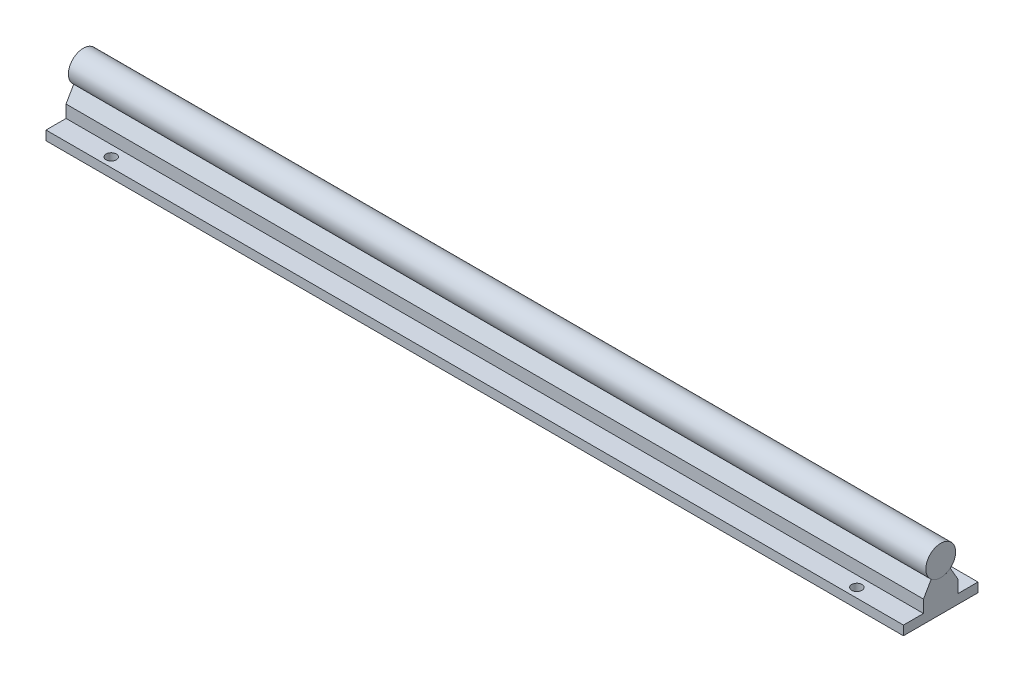
SolidWorks part; units mm, degrees
ref_plane "Спереди" through (0, 0, 0) normal (0, 0, 1) x (1, 0, 0)
ref_plane "Сверху" through (0, 0, 0) normal (0, 1, 0) x (1, 0, 0)
ref_plane "Справа" through (0, 0, 0) normal (1, 0, 0) x (0, 0, -1)
other "Центр тяжести"
sketch "Эскиз3" plane through (0, 0, 0) normal (1, 0, 0) x (0, 0, -1)
  circle A0 centre (0, 0) radius 8
  dimension "D1" = 16
extrude "Вал" add sketch "Эскиз3" along normal blind 460
sketch "Эскиз4" plane through (0, 0, 0) normal (1, 0, 0) x (0, 0, -1)
  line L0 (-9.25, -20) -> (-9.25, -13.3)
  line L1 (-20, -20) -> (-9.25, -20)
  line L2 (-20, -20) -> (-20, -25)
  line L3 (-20, -25) -> (20, -25)
  line L4 (20, -20) -> (20, -25)
  line L5 (-5.1201, -6.1469) -> (-9.25, -13.3)
  line L6 (9.25, -13.3) -> (5.1201, -6.1469)
  line L7 (9.25, -13.3) -> (9.25, -20)
  line L8 (-9.25, -13.3) -> (-20, -20) construction
  line L9 (9.25, -13.3) -> (20, -20) construction
  line L10 (0, 15.2149) -> (0, -37.056) construction
  line L11 (9.25, -20) -> (20, -20)
  line L12 (9.25, -20) -> (0, -20) construction
  line L13 (0, -20) -> (-9.25, -20) construction
  circle A0 centre (0, 0) radius 8 construction
  arc A1 (-5.1201, -6.1469) -> (5.1201, -6.1469) centre (0, 0) ccw
  point P11 (0, -25)
  dimension "D1" = 5
  dimension "D2" = 40
  dimension "D3" = 11.7
  dimension "D4" = 18.5
  dimension "D5" = 30
  dimension "D6" = 25
extrude "Опора" add sketch "Эскиз4" along normal blind 460 separate body
sketch "Эскиз5" plane through (0, -20, 0) normal (0, 1, 0) x (1, 0, 0)
  line L3 (230, 20) -> (230, -20) construction
  line L4 (460, 20) -> (0, 20) construction
  line L5 (460, -20) -> (0, -20) construction
  line L7 (430, -15) -> (30, -15) construction
  line L8 (430, -15) -> (430, 15) construction
  line L9 (430, 15) -> (30, 15) construction
  line L10 (30, -15) -> (30, 15) construction
  line L11 (430, -15) -> (30, 15) construction
  line L12 (430, 15) -> (30, -15) construction
  circle A0 centre (430, 15) radius 2.75
  circle A1 centre (430, -15) radius 2.75
  circle A2 centre (30, -15) radius 2.75
  circle A3 centre (30, 15) radius 2.75
  point P9 (230, 0)
  dimension "D1" = 5.5
  dimension "D2" = 5.5
  dimension "D5" = 5.5
  dimension "D6" = 5.5
  dimension "D3" = 400
  dimension "D4" = 30
extrude "Крепёжные отверстия" cut sketch "Эскиз5" against normal through all
ref_axis "Ось вала" through (495.3685, 0, 0) along (-1, 0, 0)
ref_axis "Ось2" through (30, -29.3693, 15) along (0, 1, 0)
ref_axis "Ось3" through (30, -29.1148, -15) along (0, 1, 0)
ref_axis "Ось4" through (430, -30.6719, 15) along (0, 1, 0)
ref_axis "Ось5" through (430, -30.284, -15) along (0, 1, 0)
